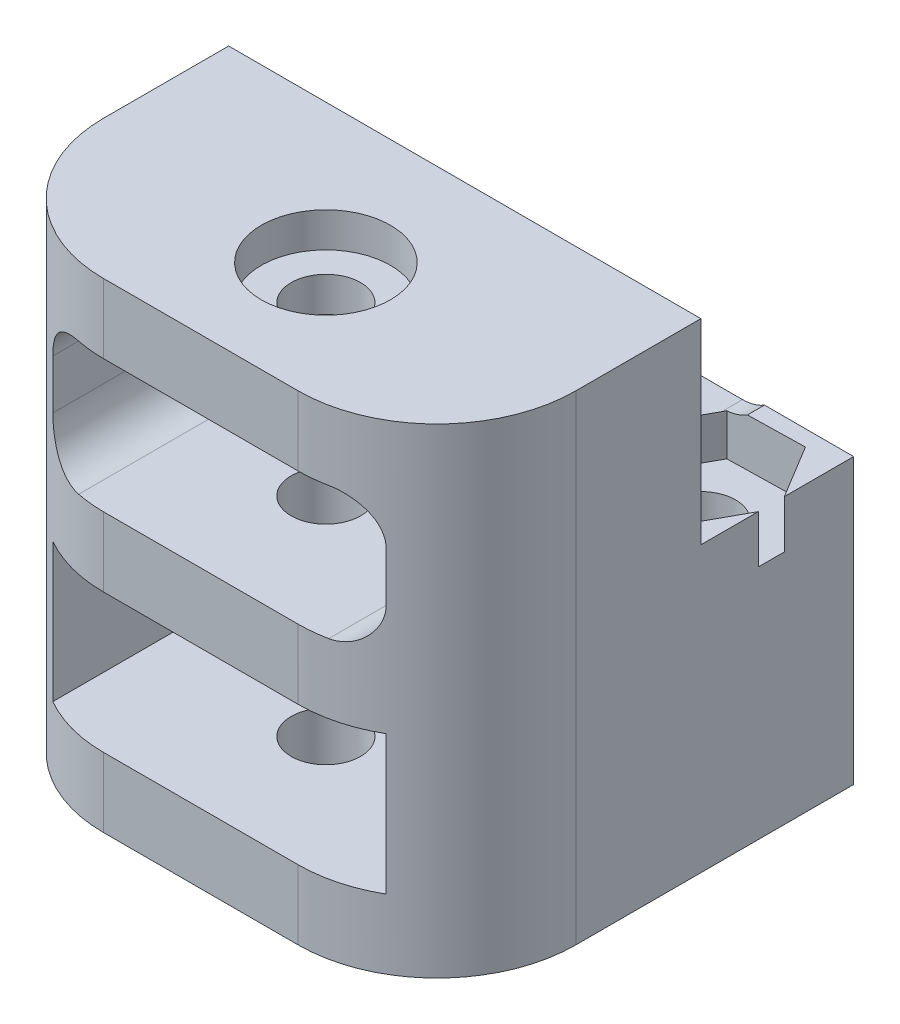
SolidWorks part; units mm, degrees
ref_plane "Alzado" through (0, 0, 0) normal (0, 0, 1) x (1, 0, 0)
ref_plane "Planta" through (0, 0, 0) normal (0, 1, 0) x (1, 0, 0)
ref_plane "Vista lateral" through (0, 0, 0) normal (1, 0, 0) x (0, 0, -1)
sketch "Croquis1" plane through (0, 0, 0) normal (0, 1, 0) x (1, 0, 0)
  line L0 (5, 0) -> (5, -30)
  line L2 (0, 0) -> (0, -30)
  line L4 (-24, 0) -> (-24, -30)
  line L6 (-29, 0) -> (-29, -30)
  line L8 (-24, -30) -> (-29, -30)
  line L9 (-29, 0) -> (-24, 0)
  line L10 (0, 0) -> (5, 0)
  line L11 (0, -30) -> (5, -30)
  line L12 (5, 5) -> (5, -35) construction
  line L13 (5, 5) -> (-29, 5) construction
  line L14 (-29, 5) -> (-29, -35) construction
  line L15 (5, -35) -> (-29, -35) construction
  line L16 (0, 0) -> (-24, 0) construction
  line L17 (0, -30) -> (-24, -30) construction
  dimension "D1" = 24
  dimension "D2" = 30
  dimension "D3" = 5
extrude "Saliente-Extruir1" add sketch "Croquis1" along normal blind 19.1 contours L8 L6 L9 L4 | L11 L0 L10 L2
sketch "Croquis2" plane through (0, 0, 0) normal (-1, 0, 0) x (0, 0, 1)
  line L0 (30, 19.1) -> (30, 0) construction
  line L1 (0, 19.1) -> (30, 19.1)
  line L2 (0, 19.1) -> (0, 14.1)
  line L3 (0, 14.1) -> (30, 14.1)
  line L4 (30, 19.1) -> (30, 14.1)
  line L5 (30, 9.55) -> (27.8572, 9.55) construction
  line L6 (0, 4.55) -> (30, 4.55)
  line L7 (30, -15.45) -> (30, 4.55)
  line L8 (0, -15.45) -> (30, -15.45)
  line L9 (0, -15.45) -> (0, 4.55)
  dimension "D1" = 5
  dimension "D2" = 20
  dimension "D3" = 5
extrude "Saliente-Extruir2" add sketch "Croquis2" along normal up to surface (24 mm away) up to face at (-24, 9.55, 15)
sketch "Croquis3" plane through (0, 19.1, 0) normal (0, 1, 0) x (1, 0, 0)
  line L0 (-12, -30) -> (-12, -21) construction
  line L1 (5, -30) -> (-29, -30) construction
  circle A0 centre (-12, -21) radius 2.5
  dimension "D1" = 5
  dimension "D2" = 9
extrude "Cortar-Extruir1" cut sketch "Croquis3" against normal up to next
sketch "Croquis4" plane through (0, 19.1, 0) normal (0, 1, 0) x (1, 0, 0)
  circle A0 centre (-12, -21) radius 4.65
  dimension "D1" = 9.3
extrude "Cortar-Extruir2" cut sketch "Croquis4" against normal blind 2.5
sketch "Croquis5" plane through (-29, 0, 0) normal (-1, 0, 0) x (0, 0, 1)
  line L0 (30, 19.1) -> (30, 0) construction
  line L1 (9.95, 19.6) -> (20.05, 19.6)
  line L2 (9.95, 19.6) -> (9.95, -0.5)
  line L3 (9.95, -0.5) -> (20.05, -0.5)
  line L4 (20.05, 19.6) -> (20.05, -0.5)
  line L5 (0, 19.1) -> (30, 19.1) construction
  line L6 (20.05, 19.6) -> (20.05, 19.1) construction
  point P6 (30, 9.55)
  point P7 (20.05, 9.55)
  point P10 (15, 19.1)
  point P11 (15, 19.6)
  dimension "D1" = 10.1
  dimension "D2" = 20.1
sketch "Croquis11" plane through (0, 0, 30) normal (0, 0, 1) x (1, 0, 0)
  line L1 (-24, -15.45) -> (0, -15.45) construction
  line L2 (-16.75, -12.45) -> (-7.25, -12.45)
  line L3 (-7.25, -12.45) -> (-7.25, -15.45)
  line L6 (-7.25, -15.45) -> (-16.75, -15.45)
  line L7 (-16.75, -15.45) -> (-16.75, -12.45)
  dimension "D1" = 9.5
  dimension "D2" = 3
  dimension "D3" = 9.5
  dimension "D4" = 3
fillet "Redondeo1" radius 10 2 edges at (-29, 9.55, 30) (5, 9.55, 30)
sketch "Croquis12" plane through (0, 4.55, 0) normal (0, 1, 0) x (1, 0, 0)
  line L0 (-29, -9) -> (-29, -7) construction
  line L2 (-24, -6) -> (-24, 0) construction
  line L3 (-29, 0) -> (5, 0) construction
  line L4 (-12, 0) -> (-12, -9) construction
  line L5 (-12, -9) -> (-29, -9) construction
  circle A0 centre (-24, -6) radius 2.5
  circle A1 centre (0, -6) radius 2.5
  dimension "D1" = 5
  dimension "D2" = 6
  dimension "D3" = 2
  dimension "D4" = 17
  dimension "D5" = 9
  dimension "D6" = 5
extrude "Cortar-Extruir8" cut sketch "Croquis12" against normal up to surface (20 mm away) up to face at (-12, -15.45, 19.6631)
fillet "Redondeo2" radius 3 4 edges at (-24, 14.1, 14.3301) (-24, 4.55, 18.5801) (0, 14.1, 14.3301) (0, 4.55, 18.5801)
sketch "Croquis14" plane through (0, 4.55, 0) normal (0, 1, 0) x (1, 0, 0)
  line L1 (-5.5413, -6.1174) -> (-2.669, -10.8576)
  line L2 (-2.669, -10.8576) -> (2.8723, -10.7402)
  line L3 (2.8723, -10.7402) -> (5.5413, -5.8826)
  line L4 (5.5413, -5.8826) -> (2.669, -1.1424)
  line L5 (2.669, -1.1424) -> (-2.8723, -1.2598)
  line L6 (-2.8723, -1.2598) -> (-5.5413, -6.1174)
  line L7 (-18.4574, -6) -> (-21.2287, -1.2)
  line L8 (-21.2287, -1.2) -> (-26.7713, -1.2)
  line L9 (-26.7713, -1.2) -> (-29.5426, -6)
  line L10 (-29.5426, -6) -> (-26.7713, -10.8)
  line L11 (-26.7713, -10.8) -> (-21.2287, -10.8)
  line L12 (-21.2287, -10.8) -> (-18.4574, -6)
  circle A0 centre (0, -6) radius 2.5 construction
  circle A1 centre (-24, -6) radius 2.5 construction
  circle A2 centre (0, -6) radius 2.5 construction
  circle A3 centre (-24, -6) radius 2.5 construction
  circle A6 centre (0, -6) radius 4.8 construction
  circle A7 centre (-24, -6) radius 4.8 construction
  dimension "D1" = 9.6
  dimension "D2" = 9.6
extrude "Cortar-Extruir10" cut sketch "Croquis14" against normal mid plane 6
sketch "Croquis15" plane through (5, 0, 0) normal (1, 0, 0) x (0, 0, -1)
  line L3 (-11, 11) -> (-11, 5)
  line L4 (-11, 5) -> (0, 5)
  line L6 (0, 19.1) -> (0, 0) construction
  line L7 (-11, 11) -> (0, 11)
  line L8 (0, 11) -> (0, 5)
  dimension "D1" = 6
  dimension "D2" = 11
extrude "Cortar-Extruir11" cut sketch "Croquis15" along direction (1, 0, 0) on the side against the normal up to surface (34 mm away) up to face at (-29, 9.55, 10)
sketch "Croquis17" plane through (0, 4.55, 0) normal (0, 1, 0) x (1, 0, 0)
  circle A0 centre (-12, -21) radius 2.5 construction
  circle A1 centre (-12, -21) radius 2.5
extrude "Cortar-Extruir14" cut sketch "Croquis17" against normal up to next
sketch "Croquis18" plane through (5, 0, 0) normal (1, 0, 0) x (0, 0, -1)
  line L1 (-11, 11) -> (0, 11)
  line L2 (-11, 11) -> (-11, 19.1)
  line L3 (-11, 19.1) -> (0, 19.1)
  line L4 (0, 11) -> (0, 19.1)
extrude "Cortar-Extruir15" cut sketch "Croquis18" against normal up to surface (34 mm away) up to face at (-29, 6.9417, 7.1667)
ref_plane "Plano1" through (0, -15.45, 0) normal (0, -1, 0) x (-1, 0, 0)
sketch "Croquis19" plane through (0, -15.45, 0) normal (0, -1, 0) x (-1, 0, 0)
  line L0 (0, -28.6603) -> (0, -8.5) construction
  line L1 (0, -3.5) -> (0, 0) construction
  line L2 (0, 0) -> (-5, 0) construction
  line L3 (-5, 0) -> (-5, -20) construction
  line L4 (24, -8.5) -> (24, -28.6603) construction
  line L5 (29, -20) -> (29, 0) construction
  line L6 (29, 0) -> (24, 0) construction
  line L7 (24, 0) -> (24, -3.5) construction
  line L8 (0, -28.6603) -> (0, -8.5)
  line L9 (0, -3.5) -> (0, 0)
  line L10 (0, 0) -> (-5, 0)
  line L11 (-5, 0) -> (-5, -20)
  line L12 (24, -8.5) -> (24, -28.6603)
  line L13 (29, -20) -> (29, 0)
  line L14 (29, 0) -> (24, 0)
  line L15 (24, 0) -> (24, -3.5)
  arc A0 (0, -3.5) -> (0, -8.5) centre (0, -6) ccw construction
  arc A1 (-5, -20) -> (0, -28.6603) centre (5, -20) ccw construction
  arc A2 (24, -8.5) -> (24, -3.5) centre (24, -6) ccw construction
  arc A3 (24, -28.6603) -> (29, -20) centre (19, -20) ccw construction
  arc A4 (0, -3.5) -> (0, -8.5) centre (0, -6) ccw
  arc A5 (-5, -20) -> (0, -28.6603) centre (5, -20) ccw
  arc A6 (24, -8.5) -> (24, -3.5) centre (24, -6) ccw
  arc A7 (24, -28.6603) -> (29, -20) centre (19, -20) ccw
extrude "Saliente-Extruir3" add sketch "Croquis19" against normal up to next
sketch "Croquis20" plane through (0, 0, 0) normal (0, 0, -1) x (-1, 0, 0)
  line L10 (0, -0.45) -> (24, -0.45)
  line L28 (0, 0) -> (0, -10.45)
  line L29 (0, -10.45) -> (24, -10.45)
  line L30 (24, -10.45) -> (24, 0)
  line L31 (21, -0.45) -> (3, -0.45)
  line L32 (0, -0.45) -> (0, -10.45)
  line L33 (0, -10.45) -> (24, -10.45)
  line L34 (24, -10.45) -> (24, -0.45)
  line L42 (24, 0) -> (23.6453, 0)
  line L46 (0.3547, 0) -> (0, 0)
  arc A6 (21, -0.45) -> (23.6453, 0) centre (21, 7.55) ccw
  arc A10 (0.3547, 0) -> (3, -0.45) centre (3, 7.55) ccw
  dimension "D2" = 5
extrude "Cortar-Extruir16" cut sketch "Croquis20" against normal up to next
